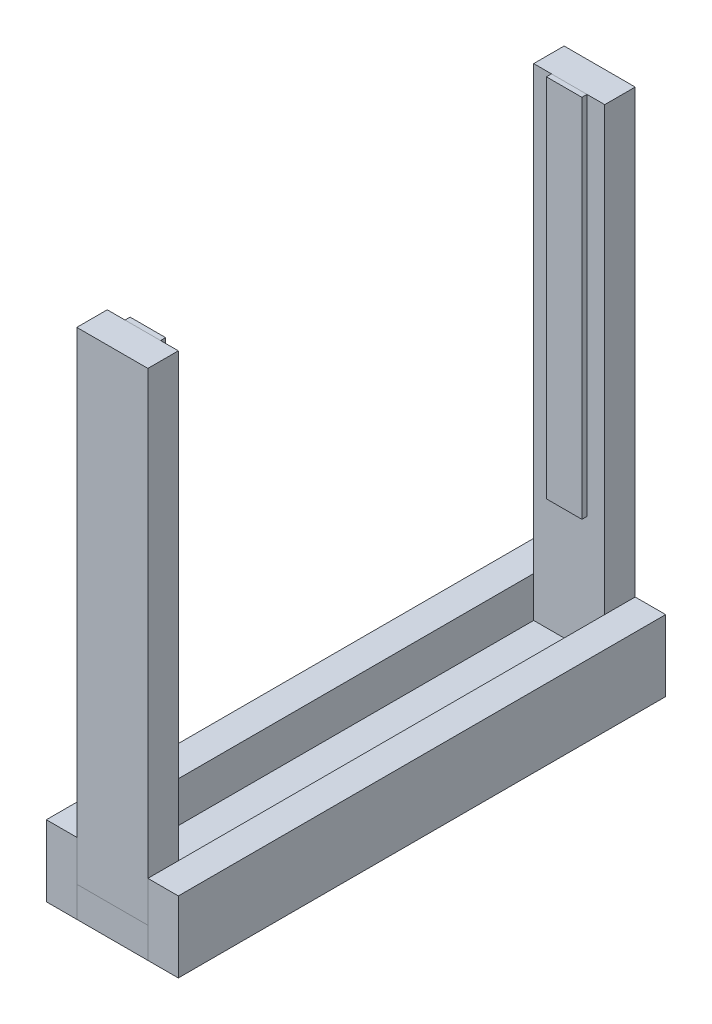
SolidWorks part; units mm, degrees
material "Oak"
ref_plane "Front Plane" through (0, 0, 0) normal (0, 0, 1) x (1, 0, 0)
ref_plane "Top Plane" through (0, 0, 0) normal (0, 1, 0) x (1, 0, 0)
ref_plane "Right Plane" through (0, 0, 0) normal (1, 0, 0) x (0, 0, -1)
sketch "Sketch1" plane through (0, 0, 0) normal (0, 1, 0) x (1, 0, 0)
  line L1 (-44.45, -304.8) -> (44.45, -304.8)
  line L2 (-44.45, -304.8) -> (-44.45, 304.8)
  line L3 (-44.45, 304.8) -> (44.45, 304.8)
  line L4 (44.45, -304.8) -> (44.45, 304.8)
  line L5 (-44.45, -304.8) -> (44.45, 304.8) construction
  line L6 (-44.45, 304.8) -> (44.45, -304.8) construction
  point P0 (0, 0)
  dimension "D1" = 609.6
  dimension "D2" = 88.9
extrude "Base Board" add sketch "Sketch1" along normal blind 38.1
sketch "Sketch2" plane through (0, 38.1, 0) normal (0, 1, 0) x (1, 0, 0)
  line L0 (-44.45, 304.8) -> (-44.45, -304.8) construction
  line L1 (44.45, -304.8) -> (-44.45, -304.8)
  line L2 (44.45, -304.8) -> (44.45, -266.7)
  line L3 (44.45, -266.7) -> (-44.45, -266.7)
  line L4 (-44.45, -304.8) -> (-44.45, -266.7)
  dimension "D1" = 38.1
extrude "Vertical Board" add sketch "Sketch2" along normal blind 603.25 separate body
mirror "Vertical Board Mirror" about plane through (0, 0, 0) normal (0, 0, 1) of bodies 102
sketch "Sketch3" plane through (44.45, 0, 0) normal (1, 0, 0) x (0, 0, -1)
  line L0 (304.8, 641.35) -> (304.8, 38.1) construction
  line L1 (-304.8, 0) -> (304.8, 0)
  line L2 (-304.8, 0) -> (-304.8, 88.9)
  line L3 (-304.8, 88.9) -> (304.8, 88.9)
  line L4 (304.8, 0) -> (304.8, 88.9)
  dimension "D1" = 88.9
extrude "Lateral Support" add sketch "Sketch3" along normal blind 38.1 separate body
mirror "Lateral Support Mirror" about plane through (0, 0, 0) normal (1, 0, 0) of bodies 104
sketch "Sketch4" plane through (0, 0, 266.7) normal (0, 0, -1) x (-1, 0, 0)
  line L0 (-44.45, 641.35) -> (44.45, 641.35) construction
  line L1 (-22.225, 641.35) -> (22.225, 641.35)
  line L2 (-22.225, 641.35) -> (-22.225, 184.15)
  line L3 (-22.225, 184.15) -> (22.225, 184.15)
  line L4 (22.225, 641.35) -> (22.225, 184.15)
  point P6 (0, 641.35)
  dimension "D1" = 457.2
  dimension "D2" = 44.45
extrude "Drawer Slide" add sketch "Sketch4" along normal blind 6.35 separate body
mirror "Mirror5" about plane through (0, 0, 0) normal (0, 0, 1) of bodies 106
